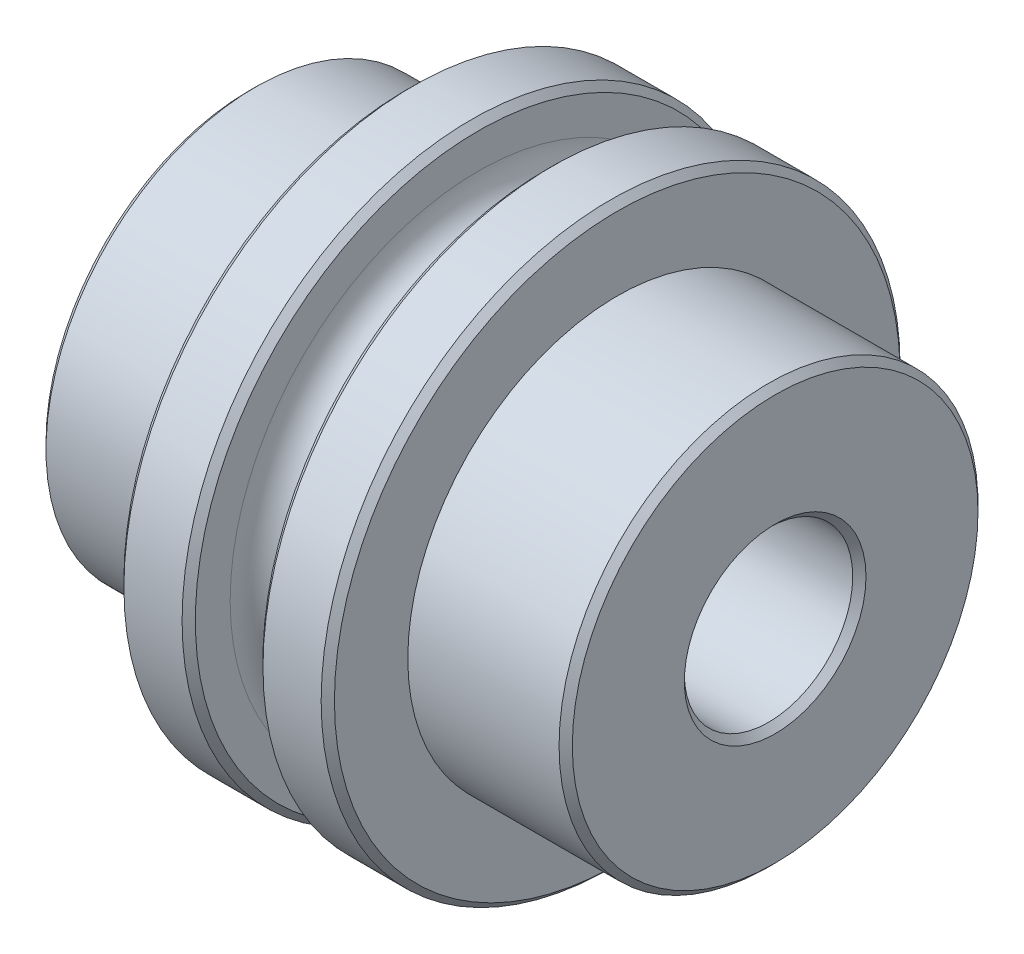
SolidWorks part; units mm, degrees
material "Nylon 101"
ref_plane "Front Plane" through (0, 0, 0) normal (0, 0, 1) x (1, 0, 0)
ref_plane "Top Plane" through (0, 0, 0) normal (0, 1, 0) x (1, 0, 0)
ref_plane "Right Plane" through (0, 0, 0) normal (1, 0, 0) x (0, 0, -1)
sketch "Sketch1" plane through (0, 0, 0) normal (1, 0, 0) x (0, 0, -1)
  circle A0 centre (0, 0) radius 12.6365
  dimension "D1" = 25.273
extrude "Boss-Extrude1" add sketch "Sketch1" along normal blind 9.525
sketch "Sketch2" plane through (0, 0, 0) normal (-1, 0, 0) x (0, 0, 1)
  circle A0 centre (0, 0) radius 17.4625
  dimension "D1" = 34.925
extrude "Boss-Extrude2" add sketch "Sketch2" along normal blind 12.7
sketch "Sketch6" plane through (0, 0, 0) normal (0, 0, 1) x (1, 0, 0)
  line L0 (-8.39, 17.4625) -> (-8.39, 14.9625)
  line L1 (0, 17.4625) -> (-12.7, 17.4625) construction
  line L2 (-4.31, 17.4625) -> (-4.31, 14.9625)
  line L3 (-6.35, 12.9225) -> (-6.35, 0) construction
  line L4 (-6.35, 14.9625) -> (-6.35, 17.4625) construction
  line L5 (-8.39, 17.4625) -> (-4.31, 17.4625)
  line L6 (-8.39, 17.4625) -> (-4.31, 17.4625)
  line L7 (-6.35, 0) -> (0, 0) construction
  line L8 (0, -17.4625) -> (0, 17.4625) construction
  arc A0 (-8.39, 14.9625) -> (-4.31, 14.9625) centre (-6.35, 14.9625) ccw
  dimension "D1" = 2.04
  dimension "D2" = 12.9225
  dimension "D3" = 2.5
  dimension "D4" = 6.35
revolve "Cut-Revolve1" cut sketch "Sketch6" angle 360 about L7 region at (-6.35, 15.3861, 0)
ref_plane "Plane1" through (-6.35, 0, 0) normal (-1, 0, 0) x (0, 0, 1)
mirror "Mirror1" about plane through (-6.35, 0, 0) normal (-1, 0, 0) of "Boss-Extrude1"
sketch "Sketch5" plane through (-22.225, 0, 0) normal (-1, 0, 0) x (0, 0, 1)
  circle A0 centre (0, 0) radius 5.08
  dimension "D1" = 10.16
extrude "Cut-Extrude3" cut sketch "Sketch5" against normal through all
chamfer "Chamfer1" distance 0.4 angle 45 8 edges at (9.525, 0, -12.6365) (9.525, 0, 5.08) (-12.7, 0, 17.4625) (-8.39, 0, 17.4625) (0, 0, 17.4625) (-4.31, 0, 17.4625) (-22.225, 0, -12.6365) (-22.225, 0, 5.08)
equation "\"D1@Sketch6\"=2mm+.04mm"
equation "\"D2@Sketch6\"=19mm/2"
equation "\"D3@Sketch6\"=2.5mm"
